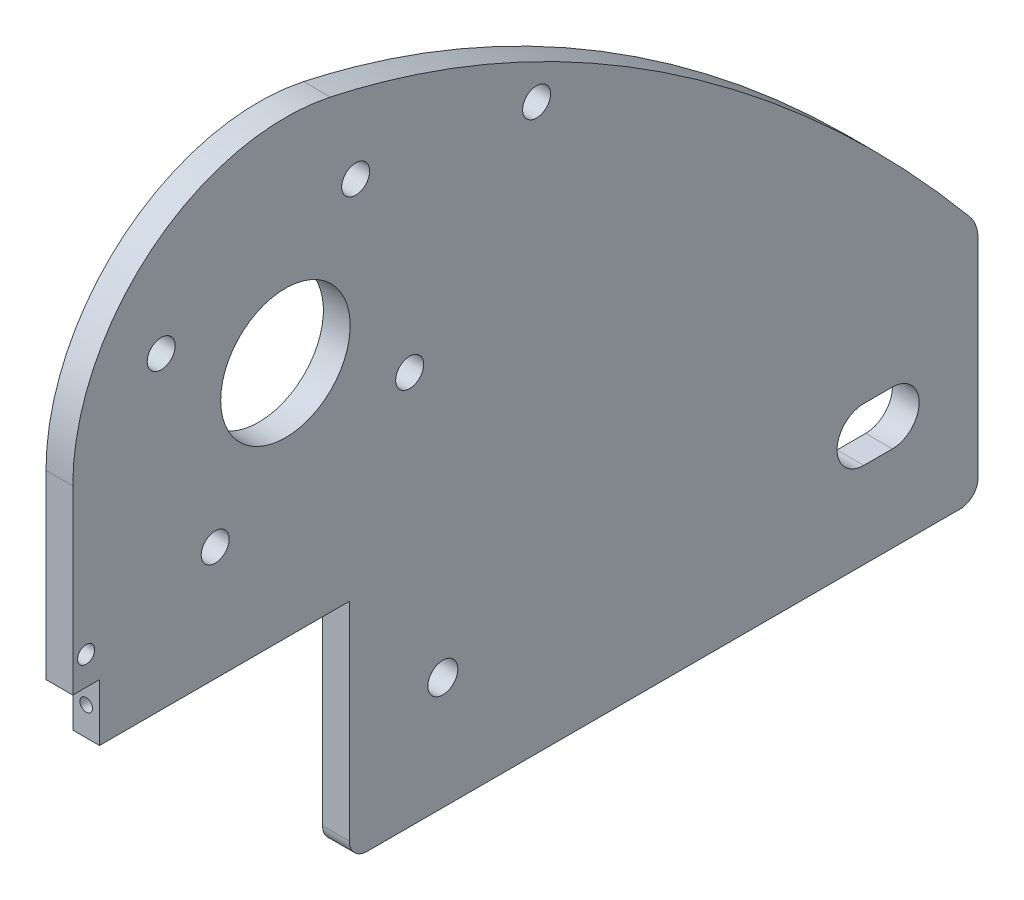
SolidWorks part; units mm, degrees
ref_plane "Front Plane" through (0, 0, 0) normal (0, 0, 1) x (1, 0, 0)
ref_plane "Top Plane" through (0, 0, 0) normal (0, 1, 0) x (1, 0, 0)
ref_plane "Right Plane" through (0, 0, 0) normal (1, 0, 0) x (0, 0, -1)
sketch "Sketch1" plane through (0, 0, 0) normal (1, 0, 0) x (0, 0, -1)
  line L0 (-28.1703, 0) -> (77.3828, 0)
  line L1 (80.5578, 3.175) -> (80.5578, 40.132)
  line L2 (-80.5578, 82.55) -> (-80.5578, 50.292)
  line L4 (-75.7953, 50.292) -> (-75.7953, 40.132)
  line L5 (-80.5578, 50.292) -> (-75.7953, 50.292)
  line L6 (65.3178, 20.066) -> (60.2378, 20.066) construction
  line L7 (-75.7953, 40.132) -> (-31.3453, 40.132)
  line L10 (-31.3453, 40.132) -> (-31.3453, 3.175)
  line L11 (-37.7935, 96.5728) -> (77.9184, 56.022) construction
  line L12 (-52.4128, 71.2982) -> (40.4331, -8.7847) construction
  line L13 (65.3178, 15.3035) -> (60.2378, 15.3035)
  line L14 (65.3178, 24.8285) -> (60.2378, 24.8285)
  arc A0 (65.3178, 15.3035) -> (65.3178, 24.8285) centre (65.3178, 20.066) ccw
  circle A1 centre (-42.7078, 82.55) radius 31.5 construction
  circle A2 centre (65.3178, 20.066) radius 76.2 construction
  circle A3 centre (65.3178, 20.066) radius 38.1 construction
  circle A4 centre (-42.7078, 82.55) radius 14.859 construction
  arc A5 (-34.6964, 119.5424) -> (-80.5578, 82.55) centre (-42.7078, 82.55) ccw
  arc A6 (-28.1703, 0) -> (-31.3453, 3.175) centre (-28.1703, 3.175) cw
  arc A7 (77.3828, 0) -> (80.5578, 3.175) centre (77.3828, 3.175) ccw
  arc A8 (80.5578, 40.132) -> (79.0888, 44.1938) centre (74.2078, 40.132) ccw
  circle A9 centre (1.9922, 100.457) radius 5.5562 construction
  circle A10 centre (-55.209, 60.4394) radius 2.4892
  circle A11 centre (-14.6922, 20.066) radius 2.667
  circle A12 centre (-20.5972, 70.0488) radius 2.4892
  circle A13 centre (-64.8184, 95.0512) radius 2.4892
  circle A14 centre (-30.2065, 104.6606) radius 2.4892
  circle A15 centre (-78.1765, 55.372) radius 1.524
  circle A16 centre (-42.7078, 82.55) radius 11.5228
  arc A17 (60.2378, 24.8285) -> (60.2378, 15.3035) centre (60.2378, 20.066) ccw
  circle A19 centre (1.9922, 100.457) radius 2.4892
  spline S0 degree 3 poles (79.0888, 44.1938) (50.6675, 78.3472) (10.808, 109.6876) (-34.6964, 119.5424) knots 0 0 0 0 1 1 1 1
  point P28 (80.5578, 40.132)
  point P39 (62.7778, 20.066)
  dimension "D4" = 9.525
  dimension "D7" = 29.718
  dimension "D8" = 63
  dimension "D9" = 6.35
  dimension "D12" = 3.175
  dimension "D13" = 6.35
  dimension "D14" = 76.2
  dimension "D15" = 152.4
  dimension "D18" = 5.334
  dimension "D19" = 4.9784
  dimension "D20" = 60.325
  dimension "D23" = 3.048
  dimension "D27" = 82.55
  dimension "D28" = 11.1125
  dimension "D29" = 4.9784
  dimension "D2" = 40.132
  dimension "D3" = 20.066
  dimension "D5" = 15.24
  dimension "D6" = 44.45
  dimension "D10" = 161.1156
  dimension "D11" = 95.25
  dimension "D17" = 25.4
  dimension "D21" = 4.7625
  dimension "D22" = 10.16
  dimension "D24" = 5.08
  dimension "D25" = 2.3813
  dimension "D26" = 5.08
  dimension "D16" = 4
extrude "Boss-Extrude1" add sketch "Sketch1" along normal blind 4.7625
sketch "Sketch2" plane through (0, 0, 75.7953) normal (0, 0, 1) x (1, 0, 0)
  line L0 (4.7625, 50.292) -> (4.7625, 40.132) construction
  line L1 (4.7625, 40.132) -> (0, 40.132) construction
  circle A0 centre (2.3813, 45.212) radius 1.1303
  point P4 (4.7625, 45.212)
  point P7 (2.3813, 40.132)
  dimension "D1" = 2.2606
extrude "Cut-Extrude1" cut sketch "Sketch2" against normal blind 6.35
